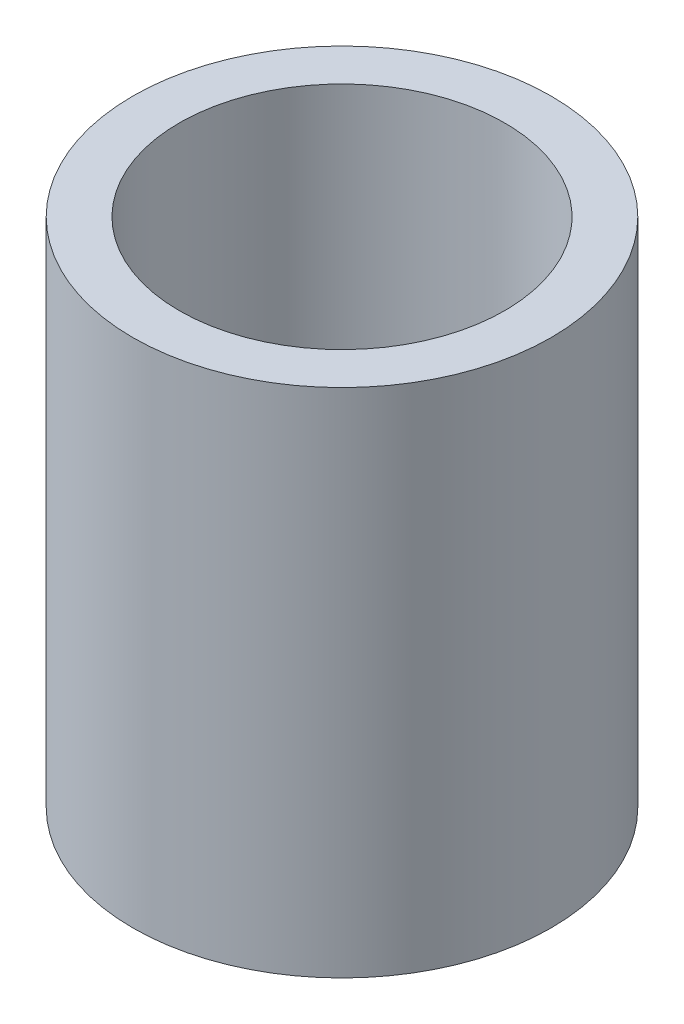
SolidWorks part; units mm, degrees
ref_plane "Front Plane" through (0, 0, 0) normal (0, 0, 1) x (1, 0, 0)
ref_plane "Top Plane" through (0, 0, 0) normal (0, 1, 0) x (1, 0, 0)
ref_plane "Right Plane" through (0, 0, 0) normal (1, 0, 0) x (0, 0, -1)
sketch "Sketch1" plane through (0, 0, 0) normal (1, 0, 0) x (0, 0, -1)
  line L0 (0, 0) -> (0, -39311.353) construction
  line L4 (25, -10.4615) -> (35, -10.4615)
  line L5 (35, -10.4615) -> (35, 89.5385)
  line L6 (35, 89.5385) -> (45, 89.5385)
  line L7 (45, 89.5385) -> (45, -20.4615)
  line L8 (45, -20.4615) -> (0, -20.4615)
  line L9 (0, -20.4615) -> (0, -10.4615)
  line L11 (0, 49.5385) -> (0, -10.4615)
  line L12 (0, -10.4615) -> (8, -10.4615) construction
  line L13 (0, 49.5385) -> (8, 49.5385)
  line L14 (8, 49.5385) -> (25, -10.4615)
  line L15 (8, 49.5385) -> (8, -10.4615) construction
  line L16 (8, -10.4615) -> (25, -10.4615) construction
  dimension "D1" = 10
  dimension "D2" = 10
  dimension "D3" = 110
  dimension "D4" = 60
  dimension "D5" = 8
  dimension "D6" = 17
revolve "Revolve1" add sketch "Sketch1" angle 360 about L0
sketch "Sketch2" plane through (0, -20.4615, 0) normal (0, -1, 0) x (1, 0, 0)
  line L0 (5.532, 5.0643) -> (40, 5.4652)
  line L1 (0, 0) -> (0, 5)
  line L2 (40, 5.4652) -> (40, -5)
  line L3 (40, -5) -> (5.5902, -5)
  circle A0 centre (0, 0) radius 5
  circle A2 centre (0, 0) radius 7.5
  point P8 (0, 0)
  point P9 (39.6996, -5)
  dimension "D1" = 10
  dimension "D2" = 15
  dimension "D3" = 40
extrude "Boss-Extrude1" add sketch "Sketch2" against normal blind 70 contours A2 L3 L2 L0 region at (23.5438, -20.4615, 0.1383)
extrude "Boss-Extrude2" add sketch "Sketch2<3>" along normal blind 10 contours A2 A0 region at (6.793, -20.4615, 2.6398)
sketch "Sketch2<3>" plane through (0, -20.4615, 0) normal (0, -1, 0) x (1, 0, 0) same geometry as "Sketch2"
extrude "Cut-Extrude1" cut sketch "Sketch2<4>" against normal blind 70 contours A0 region at (-3.4355, -20.4615, -3.4355)
sketch "Sketch2<4>" plane through (0, -20.4615, 0) normal (0, -1, 0) x (1, 0, 0) same geometry as "Sketch2"
